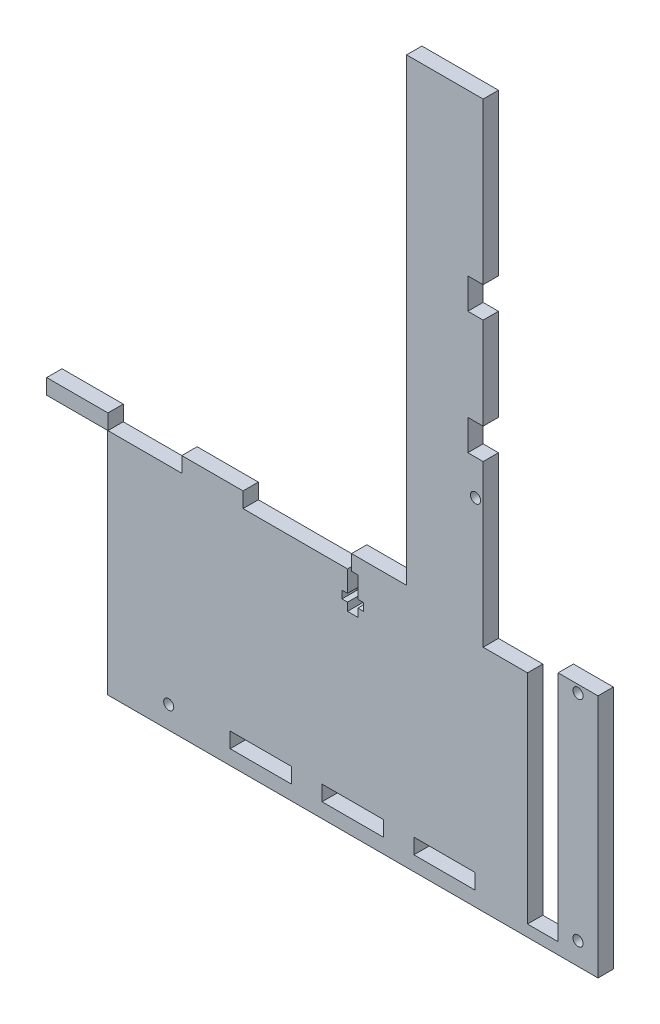
SolidWorks part; units mm, degrees
ref_plane "Front Plane" through (0, 0, 0) normal (0, 0, 1) x (1, 0, 0)
ref_plane "Top Plane" through (0, 0, 0) normal (0, 1, 0) x (1, 0, 0)
ref_plane "Right Plane" through (0, 0, 0) normal (1, 0, 0) x (0, 0, -1)
sketch "Sketch1" plane through (0, 0, 0) normal (0, 1, 0) x (1, 0, 0)
  line L0 (0, 15.4483) -> (0, 24.666) construction
  line L1 (-93.4639, 3.175) -> (110.0062, 3.175)
  line L2 (-93.4639, 3.175) -> (-93.4639, -3.175)
  line L3 (-93.4639, -3.175) -> (110.0062, -3.175)
  line L4 (110.0062, 3.175) -> (110.0062, -3.175)
  line L5 (8.1935, 0) -> (24.922, 0) construction
  arc A0 (-63.6299, 118.8222) -> (-93.1938, -3.175) centre (122.3529, 9.1717) ccw construction
  dimension "D2" = 6.35
extrude "Base Extrusion" add sketch "Sketch1" along normal up to surface (94.9689 mm away)
sketch "Sketch4" plane through (0, 0, 3.175) normal (0, 0, 1) x (1, 0, 0)
  line L0 (110.0062, 12.4189) -> (-93.1938, 12.4189) construction
  line L1 (-42.5288, 12.4189) -> (-17.1288, 12.4189)
  line L2 (-42.5288, 12.4189) -> (-42.5288, 6.0689)
  line L3 (-42.5288, 6.0689) -> (-17.1288, 6.0689)
  line L4 (-17.1288, 12.4189) -> (-17.1288, 6.0689)
  line L5 (-4.4288, 12.4189) -> (20.9712, 12.4189)
  line L6 (-4.4288, 12.4189) -> (-4.4288, 6.0689)
  line L7 (-4.4288, 6.0689) -> (20.9712, 6.0689)
  line L8 (20.9712, 12.4189) -> (20.9712, 6.0689)
  line L9 (33.6712, 12.4189) -> (59.0712, 12.4189)
  line L10 (33.6712, 12.4189) -> (33.6712, 6.0689)
  line L11 (33.6712, 6.0689) -> (59.0712, 6.0689)
  line L12 (59.0712, 12.4189) -> (59.0712, 6.0689)
  line L13 (337.8995, 6.0689) -> (110.0062, 6.0689) construction
  line L14 (110.0062, 12.4189) -> (-93.1938, 12.4189) construction
  line L15 (337.8995, 6.0689) -> (110.0062, 6.0689) construction
  line L17 (8.2712, 40.6411) -> (8.2712, -10.2729) construction
  line L18 (-93.4639, 94.9689) -> (-93.4639, 0) construction
  line L19 (110.0062, 94.9689) -> (110.0062, 0) construction
  dimension "D1" = 25.4
  dimension "D2" = 25.4
  dimension "D3" = 25.4
  dimension "D5" = 12.7
  dimension "D6" = 12.7
extrude "Tab Holes to Chassis Base" cut sketch "Sketch4" against normal through all
sketch "Sketch5" plane through (0, 0, 3.175) normal (0, 0, 1) x (1, 0, 0)
  line L0 (8.2712, 67.1576) -> (8.2712, 113.4981) construction
  line L1 (-93.4639, 94.9689) -> (-93.4639, 0) construction
  line L2 (110.0062, 94.9689) -> (110.0062, 0) construction
  line L3 (110.0062, 94.9689) -> (-93.4639, 94.9689) construction
  line B0 (10.4048, 94.9689) -> (6.1376, 94.9689)
  line B1 (6.1376, 83.0309) -> (3.8262, 83.0309)
  line B2 (3.8262, 83.0309) -> (3.8262, 86.2059)
  line B3 (3.8262, 86.2059) -> (6.1376, 86.2059)
  line B4 (6.1376, 86.2059) -> (6.1376, 94.9689)
  line B5 (6.1376, 83.0309) -> (6.1376, 79.7289)
  line B6 (6.1376, 79.7289) -> (10.4048, 79.7289)
  line B7 (10.4048, 83.0309) -> (10.4048, 79.7289)
  line B8 (10.4048, 86.2059) -> (10.4048, 94.9689)
  line B9 (12.7162, 86.2059) -> (10.4048, 86.2059)
  line B10 (12.7162, 83.0309) -> (12.7162, 86.2059)
  line B11 (10.4048, 83.0309) -> (12.7162, 83.0309)
sketch_block_instance "TSlot-1"
sketch_block "TSlot" parameters "D1"=3.302, "D2"=3.175
extrude "T Slot Center" cut sketch "Sketch5" against normal through all
sketch "Sketch6" plane through (0, 0, 3.175) normal (0, 0, 1) x (1, 0, 0)
  line L0 (110.0062, 94.9689) -> (10.4048, 94.9689) construction
  line L1 (62.3812, 94.9689) -> (30.6312, 94.9689)
  line L2 (62.3812, 94.9689) -> (62.3812, 291.8189)
  line L3 (62.3812, 291.8189) -> (30.6312, 291.8189)
  line L4 (30.6312, 94.9689) -> (30.6312, 291.8189)
  line L5 (62.3812, 12.4189) -> (62.3812, 144.9053) construction
  line L6 (56.0312, 291.8189) -> (62.3812, 291.8189) construction
  dimension "D1" = 31.75
extrude "Arm Support" add sketch "Sketch6" against normal up to surface (6.35 mm away) up to face at (8.2712, 76.0175, -3.175)
sketch "Sketch8" plane through (0, 94.9689, 0) normal (0, 1, 0) x (1, 0, 0)
  line L0 (80.775, -3.175) -> (80.775, 3.175)
  line L1 (80.775, -3.175) -> (93.475, -3.175)
  line L2 (80.775, 3.175) -> (93.475, 3.175)
  line L3 (93.475, -3.175) -> (93.475, 3.175)
  line L4 (110.0062, -3.175) -> (62.3812, -3.175) construction
  line L5 (62.3812, 3.175) -> (110.0062, 3.175) construction
  line L6 (87.125, -7.9885) -> (87.125, 24.6597) construction
extrude "Arm Clearance" cut sketch "Sketch8" against normal offset from surface (90.2064 mm away) 4.7625 up to face at (8.2712, 0, 0)
sketch "Sketch9" plane through (0, 0, 3.175) normal (0, 0, 1) x (1, 0, 0)
  line L0 (96.3524, 9.2439) -> (106.7258, 9.2439) construction
  line L3 (101.7406, 25.5557) -> (101.7406, 3.267) construction
  line L4 (93.475, 4.7625) -> (93.475, 94.9689) construction
  line L5 (110.0062, 94.9689) -> (110.0062, 0) construction
  circle A0 centre (101.7406, 9.2439) radius 2.0955
  dimension "D1" = 4.191
extrude "Base Mounting Hole 1" cut sketch "Sketch9" against normal through all
sketch "Sketch10" plane through (0, 0, 3.175) normal (0, 0, 1) x (1, 0, 0)
  line L0 (-78.6997, 9.2439) -> (-124.1873, 9.2439) construction
  line L5 (-17.1288, 12.4189) -> (-42.5288, 12.4189) construction
  line L6 (-42.5288, 6.0689) -> (-17.1288, 6.0689) construction
  line L7 (-67.9963, 38.7875) -> (-67.9963, -6.1881) construction
  line L8 (-93.4639, 94.9689) -> (-93.4639, 0) construction
  line L9 (-42.5288, 12.4189) -> (-42.5288, 6.0689) construction
  circle A0 centre (-67.9963, 9.2439) radius 2.0955
  circle A1 centre (101.7406, 9.2439) radius 2.0955 construction
extrude "Base Mounting Hole 2" cut sketch "Sketch10" against normal through all
sketch "Sketch11" plane through (0, 0, 3.175) normal (0, 0, 1) x (1, 0, 0)
  line L0 (39.2564, 147.0389) -> (78.7704, 147.0389) construction
  line L1 (62.3812, 149.1725) -> (56.0312, 149.1725) construction
  line L2 (56.0312, 144.9053) -> (62.3812, 144.9053) construction
  line L3 (59.2062, 189.1979) -> (59.2062, 134.4872) construction
  line L4 (62.3812, 291.8189) -> (62.3812, 94.9689) construction
  line L5 (56.0312, 149.1725) -> (56.0312, 161.6439) construction
  circle A0 centre (59.2062, 147.0389) radius 2.0955
  circle A1 centre (101.7406, 9.2439) radius 2.0955 construction
extrude "Arm Support Mounting Hole" cut sketch "Sketch11" against normal through all
sketch "Sketch12" plane through (0, 0, 3.175) normal (0, 0, 1) x (1, 0, 0)
  line L0 (62.3812, 94.9689) -> (62.3812, 291.8189) construction
  line L1 (56.0312, 225.1439) -> (62.3812, 225.1439)
  line L2 (56.0312, 225.1439) -> (56.0312, 212.4439)
  line L3 (56.0312, 212.4439) -> (62.3812, 212.4439)
  line L4 (62.3812, 225.1439) -> (62.3812, 212.4439)
  line L5 (56.0312, 174.3439) -> (62.3812, 174.3439)
  line L6 (56.0312, 174.3439) -> (56.0312, 161.6439)
  line L7 (56.0312, 161.6439) -> (62.3812, 161.6439)
  line L8 (62.3812, 174.3439) -> (62.3812, 161.6439)
  line L9 (56.0312, 161.6439) -> (56.0312, 174.3439) construction
  line L10 (56.0312, 174.3439) -> (62.3812, 174.3439) construction
  line L11 (62.3812, 161.6439) -> (56.0312, 161.6439) construction
  line L12 (56.0312, 212.4439) -> (56.0312, 225.1439) construction
  line L13 (56.0312, 225.1439) -> (62.3812, 225.1439) construction
  line L14 (62.3812, 212.4439) -> (56.0312, 212.4439) construction
extrude "Arm Support Tab Slots" cut sketch "Sketch12" against normal through all
sketch "Sketch13" plane through (0, 94.9689, 0) normal (0, 1, 0) x (1, 0, 0)
  line L0 (-93.4639, 3.175) -> (6.1376, 3.175) construction
  line L1 (93.475, 3.175) -> (110.0062, 3.175)
  line L2 (93.475, 3.175) -> (93.475, -3.175)
  line L3 (93.475, -3.175) -> (110.0062, -3.175)
  line L4 (110.0062, 3.175) -> (110.0062, -3.175)
  line L5 (-118.5938, 3.175) -> (-93.1938, 3.175)
  line L6 (-118.5938, 3.175) -> (-118.5938, -3.175)
  line L7 (-118.5938, -3.175) -> (-93.1938, -3.175)
  line L8 (-93.1938, 3.175) -> (-93.1938, -3.175)
  line L9 (6.1376, -3.175) -> (-93.4639, -3.175) construction
  line L10 (10.4048, 3.175) -> (30.6312, 3.175) construction
  line L11 (7.818, 3.175) -> (33.218, 3.175)
  line L12 (7.818, 3.175) -> (7.818, -3.175)
  line L13 (7.818, -3.175) -> (33.218, -3.175)
  line L14 (33.218, 3.175) -> (33.218, -3.175)
  line L15 (30.6312, -3.175) -> (10.4048, -3.175) construction
  line L16 (20.518, 19.4293) -> (20.518, -15.2554) construction
  line L17 (-62.5781, 3.175) -> (-37.1781, 3.175)
  line L18 (-62.5781, 3.175) -> (-62.5781, -3.175)
  line L19 (-62.5781, -3.175) -> (-37.1781, -3.175)
  line L20 (-37.1781, 3.175) -> (-37.1781, -3.175)
  line L21 (10.4048, 3.175) -> (10.4048, -3.175) construction
  line L22 (30.6312, 3.175) -> (30.6312, -3.175) construction
  line L23 (-105.8938, 22.3632) -> (-105.8938, -15.2554) construction
  line L28 (-49.8781, 22.3632) -> (-49.8781, -21.1411) construction
  line L29 (6.1376, 3.175) -> (6.1376, -3.175) construction
  dimension "D1" = 25.4
extrude "Top Plate Tab" add sketch "Sketch13" along normal blind 6.35
sketch "Sketch14" plane through (0, 0, 3.175) normal (0, 0, 1) x (1, 0, 0)
  line L0 (-106.0288, 71.8951) -> (-106.0288, 106.4008) construction
  line L1 (-93.4639, 94.9689) -> (-118.5938, 94.9689) construction
  line L2 (-93.4639, 94.9689) -> (-93.4639, 0) construction
  line L3 (-118.5938, 101.3189) -> (-118.5938, 94.9689) construction
  line B0 (-103.8952, 94.9689) -> (-108.1624, 94.9689)
  line B1 (-108.1624, 83.0309) -> (-110.4738, 83.0309)
  line B2 (-110.4738, 83.0309) -> (-110.4738, 86.2059)
  line B3 (-110.4738, 86.2059) -> (-108.1624, 86.2059)
  line B4 (-108.1624, 86.2059) -> (-108.1624, 94.9689)
  line B5 (-108.1624, 83.0309) -> (-108.1624, 79.7289)
  line B6 (-108.1624, 79.7289) -> (-103.8952, 79.7289)
  line B7 (-103.8952, 83.0309) -> (-103.8952, 79.7289)
  line B8 (-103.8952, 86.2059) -> (-103.8952, 94.9689)
  line B9 (-101.5838, 86.2059) -> (-103.8952, 86.2059)
  line B10 (-101.5838, 83.0309) -> (-101.5838, 86.2059)
  line B11 (-103.8952, 83.0309) -> (-101.5838, 83.0309)
sketch_block_instance "TSlot-3"
extrude "T Slot Top Corner" cut sketch "Sketch14" against normal through all rebuild error yes
sketch "Sketch15" plane through (0, 0, 3.175) normal (0, 0, 1) x (1, 0, 0)
  line L0 (101.7406, 99.797) -> (101.7406, 89.693) construction
  line L1 (93.475, 4.7625) -> (93.475, 101.3189) construction
  line L2 (110.0062, 101.3189) -> (110.0062, 0) construction
  line L3 (95.644, 98.1439) -> (106.8624, 98.1439) construction
  line L7 (62.3812, 94.9689) -> (93.475, 94.9689) construction
  line L8 (7.818, 101.3189) -> (30.6312, 101.3189) construction
  circle A0 centre (101.7406, 98.1439) radius 2.0955
  dimension "D1" = 4.191
extrude "Cut-Extrude8" cut sketch "Sketch15" against normal through all
